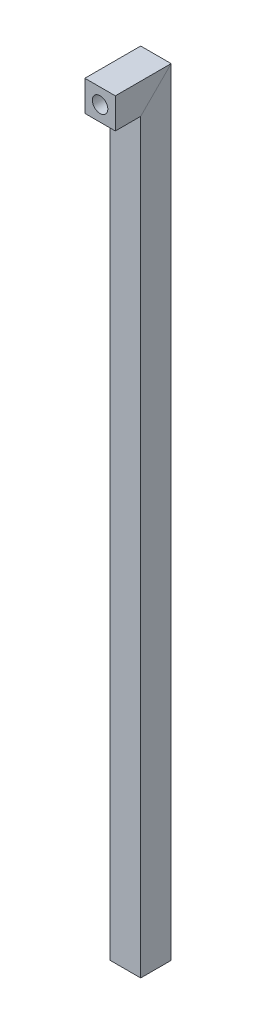
SolidWorks part; units mm, degrees
material "Custom Plastic"
ref_plane "Front Plane" through (0, 0, 0) normal (0, 0, 1) x (1, 0, 0)
ref_plane "Top Plane" through (0, 0, 0) normal (0, 1, 0) x (1, 0, 0)
ref_plane "Right Plane" through (0, 0, 0) normal (1, 0, 0) x (0, 0, -1)
sketch "Sketch1" plane through (0, 0, 0) normal (0, 0, 1) x (1, 0, 0)
  line L1 (-6, -6) -> (6, -6)
  line L2 (-6, -6) -> (-6, 6)
  line L3 (-6, 6) -> (6, 6)
  line L4 (6, -6) -> (6, 6)
  line L5 (-6, -6) -> (6, 6) construction
  line L6 (-6, 6) -> (6, -6) construction
  point P1 (0, 0)
  dimension "D1" = 12
  dimension "D2" = 12
sketch3d "3DSketch1"
  line L0 (0, 0, 0) -> (0, 0, -16)
  line L1 (0, 0, -16) -> (0, -300, -16)
  dimension "D1" = 16
  dimension "D2" = 300
sweep "Sweep1" add profiles "Sketch1" path "3DSketch1"
sketch "Sketch2" plane through (0, 0, 0) normal (0, 0, 1) x (1, 0, 0)
  circle A0 centre (0, 0) radius 3.05
  dimension "D1" = 6.1
extrude "Cut-Extrude1" cut sketch "Sketch2" against normal blind 16
ref_plane "Plane1" through (0, 0, -16) normal (0, 0, 1) x (1, 0, 0)
sketch "Sketch4" plane through (0, 0, -16) normal (0, 0, 1) x (1, 0, 0)
  line L0 (-1.6733, -2.55) -> (1.6733, -2.55)
  line L1 (1.6733, -2.55) -> (1.6733, -3.55)
  line L2 (1.6733, -3.55) -> (-1.6733, -3.55)
  line L3 (-1.6733, -3.55) -> (-1.6733, -2.55)
  circle A0 centre (0, 0) radius 3.05 construction
  circle A1 centre (0, 0) radius 3.05 construction
  dimension "D1" = 2.55
  dimension "D2" = 1
extrude "Boss-Extrude1" add sketch "Sketch4" along normal blind 10
sketch "Sketch5" plane through (0, -300, 0) normal (0, -1, 0) x (1, 0, 0)
  line L3 (6.6, -16) -> (-6.6, -16) construction
  line L4 (-5, -21) -> (5, -21)
  line L5 (-5, -21) -> (-5, -11)
  line L6 (-5, -11) -> (5, -11)
  line L7 (5, -21) -> (5, -11)
  line L8 (-5, -21) -> (5, -11) construction
  line L9 (-5, -11) -> (5, -21) construction
  line L10 (6, -10) -> (6, -22) construction
  point P0 (0, -16)
  dimension "D1" = 6
  dimension "D2" = 10
  dimension "D3" = 10
extrude "Cut-Extrude2" cut sketch "Sketch5" against normal blind 294
